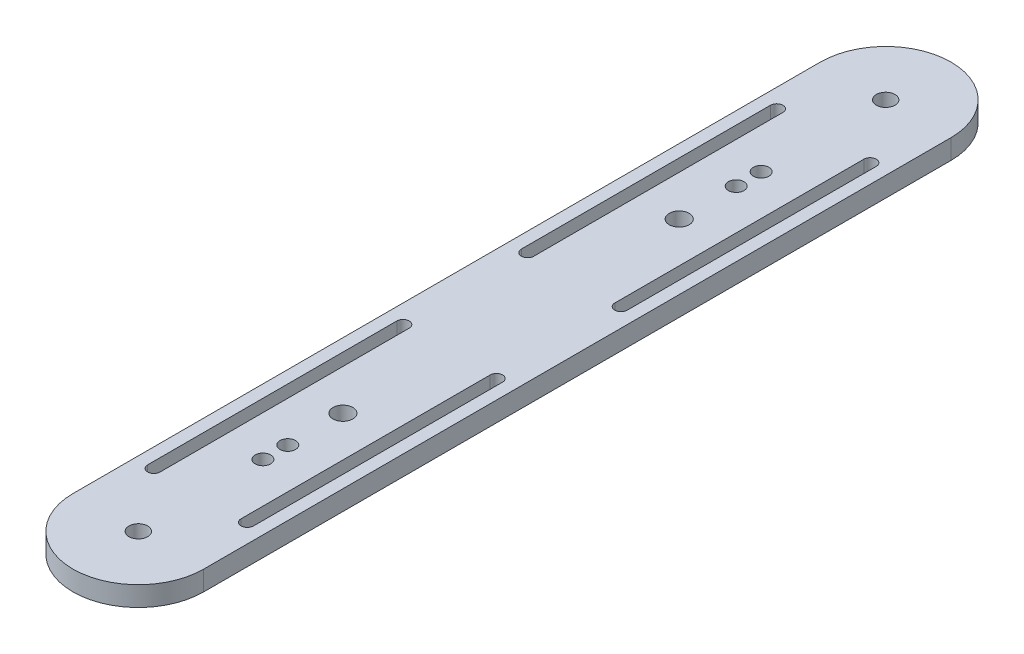
SolidWorks part; units mm, degrees
ref_plane "Front Plane" through (0, 0, 0) normal (0, 0, 1) x (1, 0, 0)
ref_plane "Top Plane" through (0, 0, 0) normal (0, 1, 0) x (1, 0, 0)
ref_plane "Right Plane" through (0, 0, 0) normal (1, 0, 0) x (0, 0, -1)
sketch "Sketch1" plane through (0, 0, 0) normal (0, 1, 0) x (1, 0, 0)
  line L0 (-10.5, 0) -> (-10.5, -120)
  line L1 (10.5, 0) -> (10.5, -120)
  arc A0 (10.5, 0) -> (-10.5, 0) centre (0, 0) ccw
  arc A1 (-10.5, -120) -> (10.5, -120) centre (0, -120) ccw
  circle A2 centre (0, 0) radius 1.5
  circle A5 centre (0, -120) radius 1.5
  dimension "D1" = 10.5
  dimension "D3" = 3
  dimension "D2" = 120
extrude "Boss-Extrude1" add sketch "Sketch1" along normal blind 3.175
sketch "Sketch2" plane through (0, 0, 0) normal (0, -1, 0) x (1, 0, 0)
  arc A0 (0, 18.75) -> (0, 21.25) centre (0, 20) ccw construction
  arc A1 (0, 21.25) -> (0, 18.75) centre (0, 20) ccw construction
  arc A2 (0, 25.25) -> (0, 22.75) centre (0, 24) ccw construction
  arc A3 (0, 22.75) -> (0, 25.25) centre (0, 24) ccw construction
  arc A4 (0, 18.75) -> (0, 21.25) centre (0, 20) ccw
  arc A5 (0, 21.25) -> (0, 18.75) centre (0, 20) ccw
  arc A6 (0, 25.25) -> (0, 22.75) centre (0, 24) ccw
  arc A7 (0, 22.75) -> (0, 25.25) centre (0, 24) ccw
extrude "Cut-Extrude1" cut sketch "Sketch2" against normal through all both and the other way through all
sketch "Sketch3" plane through (0, 3.175, 0) normal (0, 1, 0) x (1, 0, 0)
  arc A0 (0, -97.25) -> (0, -94.75) centre (0, -96) ccw construction
  arc A1 (0, -94.75) -> (0, -97.25) centre (0, -96) ccw construction
  arc A2 (0, -98.75) -> (0, -101.25) centre (0, -100) ccw construction
  arc A3 (0, -101.25) -> (0, -98.75) centre (0, -100) ccw construction
  arc A4 (0, -97.25) -> (0, -94.75) centre (0, -96) ccw
  arc A5 (0, -94.75) -> (0, -97.25) centre (0, -96) ccw
  arc A6 (0, -98.75) -> (0, -101.25) centre (0, -100) ccw
  arc A7 (0, -101.25) -> (0, -98.75) centre (0, -100) ccw
extrude "Cut-Extrude2" cut sketch "Sketch3" against normal through all both and the other way through all
sketch "Sketch4" plane through (0, 3.175, 0) normal (0, 1, 0) x (1, 0, 0)
  circle A0 centre (0, -33.15) radius 1.6 construction
  circle A1 centre (0, -87.15) radius 1.6 construction
  circle A2 centre (0, -33.15) radius 1.6
  circle A3 centre (0, -87.15) radius 1.6
extrude "Cut-Extrude3" cut sketch "Sketch4" against normal through all both and the other way through all
sketch "Sketch5" plane through (0, 0, 0) normal (0, -1, 0) x (1, 0, 0)
  line L0 (0, -10.5) -> (0, 130.5) construction
  line L1 (-10.5, 60) -> (10.5, 60) construction
  line L2 (-10.5, 0) -> (-10.5, 120) construction
  line L3 (10.5, 120) -> (10.5, 0) construction
  line L6 (-8.5, 10) -> (-8.5, 50)
  line L7 (-6.5, 50) -> (-6.5, 10)
  line L8 (6.5, 50) -> (6.5, 10)
  line L9 (8.5, 10) -> (8.5, 50)
  line L22 (8.5, 110) -> (8.5, 70)
  line L23 (6.5, 70) -> (6.5, 110)
  line L24 (-6.5, 70) -> (-6.5, 110)
  line L25 (-8.5, 110) -> (-8.5, 70)
  arc A0 (-10.5, 0) -> (10.5, 0) centre (0, 0) ccw construction
  arc A1 (10.5, 120) -> (-10.5, 120) centre (0, 120) ccw construction
  arc A4 (-8.5, 10) -> (-6.5, 10) centre (-7.5, 10) ccw
  arc A5 (-6.5, 50) -> (-8.5, 50) centre (-7.5, 50) ccw
  arc A6 (6.5, 50) -> (8.5, 50) centre (7.5, 50) cw
  arc A7 (8.5, 10) -> (6.5, 10) centre (7.5, 10) cw
  arc A20 (8.5, 110) -> (6.5, 110) centre (7.5, 110) ccw
  arc A21 (6.5, 70) -> (8.5, 70) centre (7.5, 70) ccw
  arc A22 (-6.5, 70) -> (-8.5, 70) centre (-7.5, 70) cw
  arc A23 (-8.5, 110) -> (-6.5, 110) centre (-7.5, 110) cw
  dimension "D1" = 40
  dimension "D3" = 10
  dimension "D2" = 2
  dimension "D4" = 3
extrude "Cut-Extrude4" cut sketch "Sketch5" against normal blind 40
